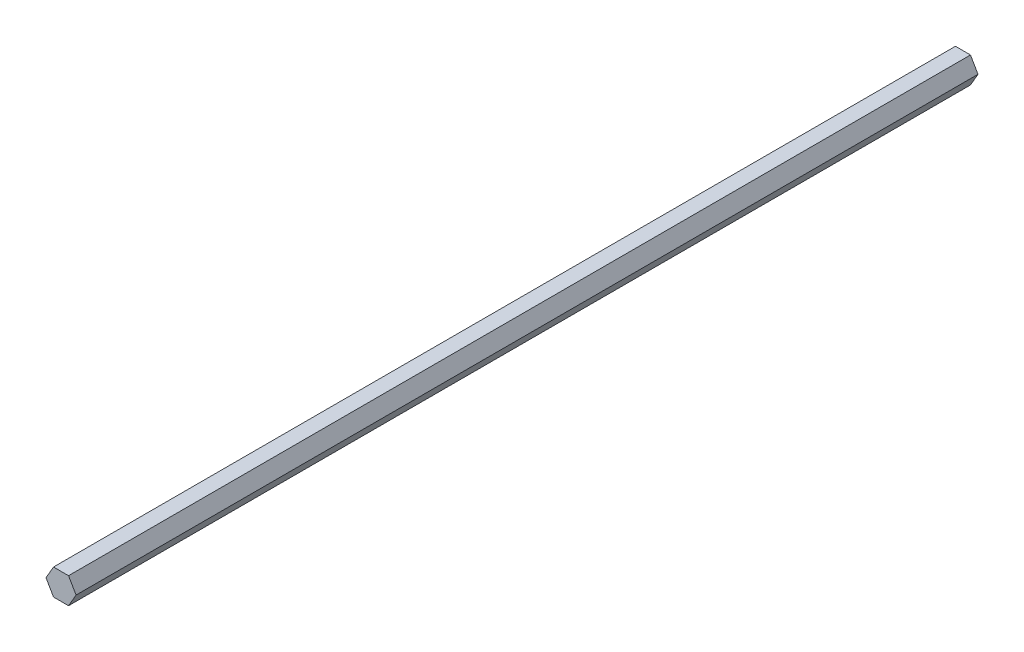
SolidWorks part; units mm, degrees
ref_plane "Front Plane" through (0, 0, 0) normal (0, 0, 1) x (1, 0, 0)
ref_plane "Top Plane" through (0, 0, 0) normal (0, 1, 0) x (1, 0, 0)
ref_plane "Right Plane" through (0, 0, 0) normal (1, 0, 0) x (0, 0, -1)
sketch "Sketch1" plane through (0, 0, 0) normal (0, 0, 1) x (1, 0, 0)
  line L1 (-3.6662, 0) -> (-1.8331, -3.175)
  line L2 (-1.8331, -3.175) -> (1.8331, -3.175)
  line L3 (1.8331, -3.175) -> (3.6662, 0)
  line L4 (3.6662, 0) -> (1.8331, 3.175)
  line L5 (1.8331, 3.175) -> (-1.8331, 3.175)
  line L6 (-1.8331, 3.175) -> (-3.6662, 0)
  circle A0 centre (0, 0) radius 3.175 construction
  dimension "D1" = 6.35
extrude "Boss-Extrude1" add sketch "Sketch1" along normal blind 220
sketch "Sketch2" plane through (0, 0, 0) normal (1, 0, 0) x (0, 0, -1)
  line L0 (0, 0) -> (-248.5563, 0) construction
ref_axis "Axis1" through (0, 0, 0) along (0, 0, 1)
